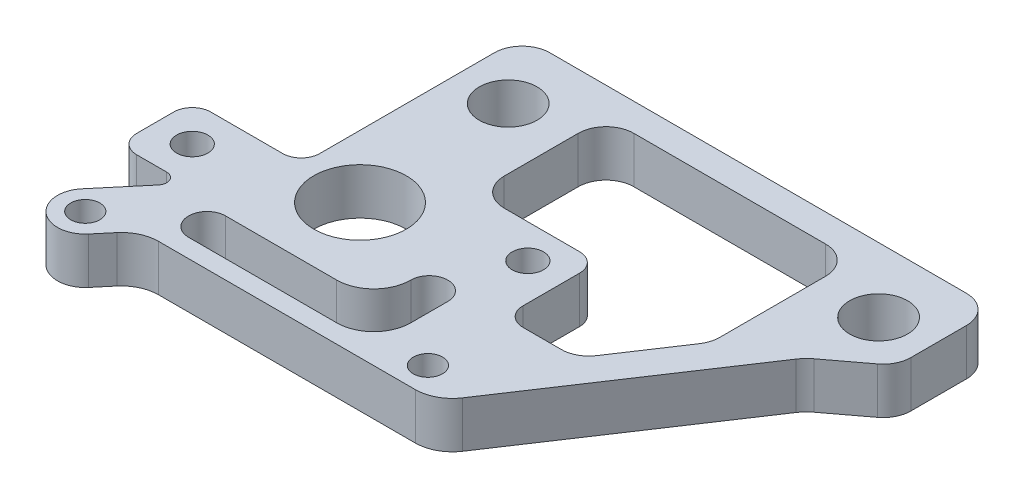
SolidWorks part; units mm, degrees
other "Markup1"
sketch "Sketch6" plane through (-23.3268, 0, -30.7975) normal (-0.0348, 0.9994, -0.0028) x (-0.9993, -0.0348, 0.0153)
sketch "Sketch7" plane through (-23.3268, 0, -30.7975) normal (-0.0348, 0.9994, -0.0028) x (-0.9993, -0.0348, 0.0153)
sketch "Sketch8" plane through (-23.3268, 0, -30.7975) normal (-0.0348, 0.9994, -0.0028) x (-0.9993, -0.0348, 0.0153)
sketch "Sketch10" plane through (-23.3268, 0, -30.7975) normal (-0.0348, 0.9994, -0.0028) x (-0.9993, -0.0348, 0.0153)
sketch "Sketch13" plane through (-23.3268, 0, -30.7975) normal (-0.0348, 0.9994, -0.0028) x (-0.9993, -0.0348, 0.0153)
sketch "Sketch15" plane through (-23.3268, 0, -30.7975) normal (-0.0348, 0.9994, -0.0028) x (-0.9993, -0.0348, 0.0153)
sketch "Sketch16" [suppressed] plane through (-23.3268, 0, -30.7975) normal (-0.0348, 0.9994, -0.0028) x (-0.9993, -0.0348, 0.0153)
sketch "Sketch17" plane through (-23.3268, 0, -30.7975) normal (-0.0348, 0.9994, -0.0028) x (-0.9993, -0.0348, 0.0153)
sketch "Sketch18" plane through (-23.3268, 0, -30.7975) normal (-0.0348, 0.9994, -0.0028) x (-0.9993, -0.0348, 0.0153)
sketch "Sketch19" [suppressed] plane through (-23.3268, 0, -30.7975) normal (-0.0348, 0.9994, -0.0028) x (-0.9993, -0.0348, 0.0153)
sketch "Sketch21" plane through (-23.3268, 0, -30.7975) normal (-0.0348, 0.9994, -0.0028) x (-0.9993, -0.0348, 0.0153)
sketch "Sketch23" plane through (-23.3268, 0, -30.7975) normal (-0.0348, 0.9994, -0.0028) x (-0.9993, -0.0348, 0.0153)
sketch "Sketch24" plane through (-23.3268, 0, -30.7975) normal (-0.0348, 0.9994, -0.0028) x (-0.9993, -0.0348, 0.0153)
sketch "Sketch25" plane through (-23.3268, 0, -30.7975) normal (-0.0348, 0.9994, -0.0028) x (-0.9993, -0.0348, 0.0153)
sketch "Sketch26" [suppressed] plane through (-23.3268, 0, -30.7975) normal (-0.0348, 0.9994, -0.0028) x (-0.9993, -0.0348, 0.0153)
sketch "Sketch27" plane through (-23.3268, 0, -30.7975) normal (-0.0348, 0.9994, -0.0028) x (-0.9993, -0.0348, 0.0153)
sketch "Sketch28" plane through (-23.3268, 0, -30.7975) normal (-0.0348, 0.9994, -0.0028) x (-0.9993, -0.0348, 0.0153)
sketch "Sketch29" plane through (-23.3268, 0, -30.7975) normal (-0.0348, 0.9994, -0.0028) x (-0.9993, -0.0348, 0.0153)
sketch "Sketch30" plane through (-23.3268, 0, -30.7975) normal (-0.0348, 0.9994, -0.0028) x (-0.9993, -0.0348, 0.0153)
sketch "Sketch32" plane through (-23.3268, 0, -30.7975) normal (-0.0348, 0.9994, -0.0028) x (-0.9993, -0.0348, 0.0153)
sketch "Sketch34" [suppressed] plane through (-23.3268, 0, -30.7975) normal (-0.0348, 0.9994, -0.0028) x (-0.9993, -0.0348, 0.0153)
sketch "Sketch35" [suppressed] plane through (-23.3268, 0, -30.7975) normal (-0.0348, 0.9994, -0.0028) x (-0.9993, -0.0348, 0.0153)
sketch "Sketch36" [suppressed] plane through (-23.3268, 0, -30.7975) normal (-0.0348, 0.9994, -0.0028) x (-0.9993, -0.0348, 0.0153)
sketch "Sketch37" plane through (-23.3268, 0, -30.7975) normal (-0.0348, 0.9994, -0.0028) x (-0.9993, -0.0348, 0.0153)
sketch "Sketch38" plane through (-23.3268, 0, -30.7975) normal (-0.0348, 0.9994, -0.0028) x (-0.9993, -0.0348, 0.0153)
sketch "Sketch39" [suppressed] plane through (-23.3268, 0, -30.7975) normal (-0.0348, 0.9994, -0.0028) x (-0.9993, -0.0348, 0.0153)
sketch "Sketch40" plane through (-23.3268, 0, -30.7975) normal (-0.0348, 0.9994, -0.0028) x (-0.9993, -0.0348, 0.0153)
sketch "Sketch41" plane through (-23.3268, 0, -30.7975) normal (-0.0348, 0.9994, -0.0028) x (-0.9993, -0.0348, 0.0153)
sketch "Sketch42" plane through (-23.3268, 0, -30.7975) normal (-0.0348, 0.9994, -0.0028) x (-0.9993, -0.0348, 0.0153)
sketch "Sketch43" plane through (-23.3268, 0, -30.7975) normal (-0.0348, 0.9994, -0.0028) x (-0.9993, -0.0348, 0.0153)
sketch "Sketch44" plane through (-23.3268, 0, -30.7975) normal (-0.0348, 0.9994, -0.0028) x (-0.9993, -0.0348, 0.0153)
sketch "Sketch45" plane through (-23.3268, 0, -30.7975) normal (-0.0348, 0.9994, -0.0028) x (-0.9993, -0.0348, 0.0153)
sketch "Sketch46" plane through (-23.3268, 0, -30.7975) normal (-0.0348, 0.9994, -0.0028) x (-0.9993, -0.0348, 0.0153)
sketch "Sketch47" plane through (-23.3268, 0, -30.7975) normal (-0.0348, 0.9994, -0.0028) x (-0.9993, -0.0348, 0.0153)
sketch "Sketch48" plane through (-23.3268, 0, -30.7975) normal (-0.0348, 0.9994, -0.0028) x (-0.9993, -0.0348, 0.0153)
sketch "Sketch49" plane through (-23.3268, 0, -30.7975) normal (-0.0348, 0.9994, -0.0028) x (-0.9993, -0.0348, 0.0153)
sketch "Sketch50" plane through (-23.3268, 0, -30.7975) normal (-0.0348, 0.9994, -0.0028) x (-0.9993, -0.0348, 0.0153)
sketch "Sketch51" plane through (-23.3268, 0, -30.7975) normal (-0.0348, 0.9994, -0.0028) x (-0.9993, -0.0348, 0.0153)
sketch "Sketch52" [suppressed] plane through (-23.3268, 0, -30.7975) normal (-0.0348, 0.9994, -0.0028) x (-0.9993, -0.0348, 0.0153)
sketch "Sketch53" [suppressed] plane through (-23.3268, 0, -30.7975) normal (-0.0348, 0.9994, -0.0028) x (-0.9993, -0.0348, 0.0153)
sketch "Sketch54" [suppressed] plane through (-23.3268, 0, -30.7975) normal (-0.0348, 0.9994, -0.0028) x (-0.9993, -0.0348, 0.0153)
sketch "Sketch55" [suppressed] plane through (-23.3268, 0, -30.7975) normal (-0.0348, 0.9994, -0.0028) x (-0.9993, -0.0348, 0.0153)
sketch "Sketch56" plane through (-23.3268, 0, -30.7975) normal (-0.0348, 0.9994, -0.0028) x (-0.9993, -0.0348, 0.0153)
sketch "Sketch57" plane through (-23.3268, 0, -30.7975) normal (-0.0348, 0.9994, -0.0028) x (-0.9993, -0.0348, 0.0153)
sketch "Sketch58" plane through (-23.3268, 0, -30.7975) normal (-0.0348, 0.9994, -0.0028) x (-0.9993, -0.0348, 0.0153)
sketch "Sketch59" plane through (-23.3268, 0, -30.7975) normal (-0.0348, 0.9994, -0.0028) x (-0.9993, -0.0348, 0.0153)
sketch "Sketch60" plane through (-23.3268, 0, -30.7975) normal (-0.0348, 0.9994, -0.0028) x (-0.9993, -0.0348, 0.0153)
sketch "Sketch61" plane through (-23.3268, 0, -30.7975) normal (-0.0348, 0.9994, -0.0028) x (-0.9993, -0.0348, 0.0153)
sketch "Sketch62" [suppressed] plane through (-23.3268, 0, -30.7975) normal (-0.0348, 0.9994, -0.0028) x (-0.9993, -0.0348, 0.0153)
sketch "Sketch63" [suppressed] plane through (-23.3268, 0, -30.7975) normal (-0.0348, 0.9994, -0.0028) x (-0.9993, -0.0348, 0.0153)
sketch "Sketch64" plane through (-24.0303, 0, -30.7975) normal (-0.0348, 0.9994, -0.0028) x (-0.9993, -0.0348, 0.0153)
sketch "Sketch65" plane through (-24.0303, 0, -30.7975) normal (-0.0348, 0.9994, -0.0028) x (-0.9993, -0.0348, 0.0153)
sketch "Sketch66" plane through (-24.0303, 0, -30.7975) normal (-0.0348, 0.9994, -0.0028) x (-0.9993, -0.0348, 0.0153)
sketch "Sketch67" [suppressed] plane through (-24.0303, 0, -30.7975) normal (-0.0348, 0.9994, -0.0028) x (-0.9993, -0.0348, 0.0153)
sketch "Sketch68" plane through (-24.0303, 0, -30.7975) normal (-0.0348, 0.9994, -0.0028) x (-0.9993, -0.0348, 0.0153)
sketch "Sketch69" plane through (-24.0303, 0, -30.7975) normal (-0.0348, 0.9994, -0.0028) x (-0.9993, -0.0348, 0.0153)
sketch "Sketch70" plane through (-24.0303, 0, -30.7975) normal (-0.0348, 0.9994, -0.0028) x (-0.9993, -0.0348, 0.0153)
sketch "Sketch71" plane through (-24.0303, 0, -30.7975) normal (-0.0348, 0.9994, -0.0028) x (-0.9993, -0.0348, 0.0153)
sketch "Sketch72" plane through (-24.0303, 0, -30.7975) normal (-0.0348, 0.9994, -0.0028) x (-0.9993, -0.0348, 0.0153)
sketch "Sketch73" [suppressed] plane through (-23.3268, 0, -30.7975) normal (-0.0348, 0.9994, -0.0028) x (-0.9993, -0.0348, 0.0153)
sketch "Sketch74" [suppressed] plane through (-24.0303, 0, -30.7975) normal (-0.0348, 0.9994, -0.0028) x (-0.9993, -0.0348, 0.0153)
sketch "Sketch75" [suppressed] plane through (-24.0303, 0, -30.7975) normal (-0.0348, 0.9994, -0.0028) x (-0.9993, -0.0348, 0.0153)
sketch "Sketch76" [suppressed] plane through (-24.0303, 0, -30.7975) normal (-0.0348, 0.9994, -0.0028) x (-0.9993, -0.0348, 0.0153)
sketch "Sketch77" plane through (-24.0303, 0, -30.7975) normal (-0.0348, 0.9994, -0.0028) x (-0.9993, -0.0348, 0.0153)
sketch "Sketch78" plane through (-23.5217, 0, -30.7975) normal (-0.0348, 0.9994, -0.0028) x (-0.9993, -0.0348, 0.0153)
sketch "Sketch79" plane through (-23.5217, 0, -30.7975) normal (-0.0348, 0.9994, -0.0028) x (-0.9993, -0.0348, 0.0153)
material "6061-T6 (SS)"
ref_plane "X-Y Datum" through (0, 0, 0) normal (0, 0, 1) x (1, 0, 0)
ref_plane "X-Z Datum" through (0, 0, 0) normal (0, 1, 0) x (1, 0, 0)
ref_plane "Y-Z Datum" through (0, 0, 0) normal (1, 0, 0) x (0, 0, -1)
other "Graphic1"
other "Graphic (Closed) -1"
other "Graphic (Closed) -2"
sketch "Sketch2" plane through (0, 0, 0) normal (0, 1, 0) x (1, 0, 0)
  line L0 (48.6426, -18.7325) -> (-23.0162, -18.7325)
  line L1 (24.0125, -14.7036) -> (25.7865, -13.7801) construction
  line L2 (0, 0) -> (105.5557, -202.7707) construction
  line L3 (11.142, -21.4036) -> (-3.5026, -29.027) construction
  line L4 (0, 0) -> (0, -121.3797) construction
  line L5 (-3.5026, -29.027) -> (90.9112, -210.3941) construction
  line L6 (90.9112, -210.3941) -> (105.5557, -202.7707) construction
  line L7 (11.142, -21.4036) -> (24.0125, -14.7036) construction
  line L11 (-12.7, 30.7975) -> (57.15, 30.7975)
  line L12 (57.15, 13.0175) -> (57.15, 30.7975)
  line L13 (57.15, 13.0175) -> (-12.7, 13.0175) construction
  line L15 (44.7685, -18.0975) -> (44.7685, -11.3157) construction
  line L16 (44.7685, -18.0975) -> (34.8625, -18.0975) construction
  line L18 (44.7685, 9.8425) -> (34.8625, 9.8425) construction
  line L20 (44.7685, -11.3157) -> (49.8485, -11.3157) construction
  line L21 (49.8485, -11.3157) -> (49.8485, 3.0607) construction
  line L22 (49.8485, 3.0607) -> (44.7685, 3.0607) construction
  line L23 (44.7685, 3.0607) -> (44.7685, 9.8425) construction
  line L24 (34.8625, -18.0975) -> (34.8625, 9.8425) construction
  line L25 (48.6426, -18.7325) -> (57.15, 13.0175)
  line L26 (-12.7, 30.7975) -> (-12.7, 13.0175)
  line L28 (-12.5603, 0) -> (-16.51, -40.5272) construction
  line L30 (-23.0162, -18.7325) -> (-12.7, 13.0175)
  circle A0 centre (0, 0) radius 3.175
  circle A1 centre (24.0125, -14.7036) radius 2
  circle A2 centre (-1.5875, 21.9075) radius 3.9688
  circle A3 centre (49.2125, 21.9075) radius 3.9687
  circle A4 centre (39.8485, -4.1275) radius 5.1
  circle A5 centre (24.0125, -14.7036) radius 3.175 construction
  circle A6 centre (39.8485, -14.6275) radius 1.6
  circle A7 centre (39.8485, 6.3725) radius 1.6
  circle A8 centre (-17.2047, -14.9225) radius 3.175 construction
  circle A9 centre (-17.2047, -14.9225) radius 2
  point P9 (11.142, -21.4036)
  point P30 (49.8485, -4.1275)
  point P31 (34.8625, -4.1275)
  dimension "D1" = 6.35
  dimension "D8" = 4
  dimension "D10" = 7.9375
  dimension "D11" = 7.9375
  dimension "D16" = 27.94
  dimension "D23" = 10.2
  dimension "D20" = 6.35
  dimension "D30" = 3.2
  dimension "D32" = 3.2
  dimension "D34" = 6.35
  dimension "D35" = 4
  dimension "D3" = 13.0175
  dimension "D4" = 16.51
  dimension "D5" = 228.6
  dimension "D6" = 24.13
  dimension "D7" = 27.5
  dimension "D9" = 16.51
  dimension "D12" = 8.89
  dimension "D13" = 69.85
  dimension "D14" = 7.9375
  dimension "D15" = 31.75
  dimension "D17" = 17.78
  dimension "D18" = 3.175
  dimension "D19" = 14.986
  dimension "D21" = 5.08
  dimension "D22" = 14.3764
  dimension "D24" = 10
  dimension "D25" = 36.83
  dimension "D26" = 50.8
  dimension "D27" = 165
  dimension "D28" = 12.7
  dimension "D29" = 17.3015
  dimension "D31" = 10.5
  dimension "D33" = 10.5
  dimension "D36" = 162
extrude "Boss-Extrude1" [suppressed] add sketch "Sketch2" against normal blind 6.35
ref_point "Point1" [suppressed]
sketch "Sketch3" [suppressed] plane through (0, 0, 0) normal (0, 1, 0) x (1, 0, 0)
  line L0 (39.9681, 6.3725) -> (39.9681, -4.1275) construction
  line L1 (57.2697, 12.9663) -> (-12.5803, 12.9663) construction
  line L5 (39.9681, -4.1275) -> (39.9681, -14.6275) construction
  line L6 (42.0297, -18.7325) -> (20.4164, -18.7325)
  line L7 (57.2697, 12.9663) -> (57.2697, 30.7975)
  line L8 (57.2697, 30.7975) -> (-12.5803, 30.7975)
  line L9 (-12.5803, 30.7975) -> (-12.5803, 12.9663)
  line L10 (40.938, 24.6176) -> (16.9472, 10.7666)
  line L11 (13.3942, 11.8528) -> (6.9035, 25.1608)
  line L12 (8.045, 26.9875) -> (40.303, 26.9875)
  line L13 (57.2697, 12.9663) -> (48.3797, 12.9663)
  line L14 (48.3797, 12.9663) -> (48.3797, -12.3825)
  line L16 (-23.0162, -18.7325) -> (48.6426, -18.7325) construction
  line L18 (16.6064, -14.8627) -> (10.2787, -14.8627)
  line L21 (-8.965, -15.5427) -> (-15.106, -18.7325)
  line L24 (-21.1701, -13.6017) -> (-12.5803, 12.9663)
  line L29 (17.8764, -16.1925) -> (17.8764, -16.1327)
  circle A0 centre (0.1197, 0) radius 3.175
  circle A1 centre (-1.4678, 21.9075) radius 3.9688
  circle A2 centre (49.3322, 21.9075) radius 3.9687
  circle A3 centre (39.9681, -4.1275) radius 5.1
  circle A4 centre (39.9681, -14.6275) radius 1.6
  circle A5 centre (39.9681, 6.3725) radius 1.6
  circle A6 centre (24.1322, -14.7036) radius 2
  circle A7 centre (-17.085, -14.9225) radius 2
  arc A8 (13.3942, 11.8528) -> (16.9472, 10.7666) centre (15.6772, 12.9663) ccw
  arc A9 (8.045, 26.9875) -> (6.9035, 25.1608) centre (8.045, 25.7175) ccw
  arc A10 (40.938, 24.6176) -> (40.303, 26.9875) centre (40.303, 25.7175) ccw
  arc A11 (10.2787, -14.8627) -> (-8.965, -15.5427) centre (0.1197, 0) cw
  arc A12 (-15.106, -18.7325) -> (-21.1701, -13.6017) centre (-17.085, -14.9225) cw
  arc A13 (42.0297, -18.7325) -> (48.3797, -12.3825) centre (42.0297, -12.3825) ccw
  arc A14 (20.4164, -18.7325) -> (17.8764, -16.1925) centre (20.4164, -16.1925) cw
  arc A15 (16.6064, -14.8627) -> (17.8764, -16.1327) centre (16.6064, -16.1327) cw
  dimension "D1" = 6.35
  dimension "D4" = 7.9375
  dimension "D9" = 10.2
  dimension "D10" = 3.2
  dimension "D11" = 4
  dimension "D21" = 2.54
  dimension "D22" = 1.27
  dimension "D3" = 6.35
  dimension "D28" = 2.54
  dimension "D29" = 1.27
  dimension "D2" = 7.9375
  dimension "D5" = 50.8
  dimension "D6" = 21.9075
  dimension "D7" = 1.5875
  dimension "D8" = 8.89
  dimension "D12" = 10.5
  dimension "D13" = 17.2047
  dimension "D14" = 24.0125
  dimension "D15" = 14.7036
  dimension "D16" = 39.8485
  dimension "D17" = 4.1275
  dimension "D18" = 14.9225
  dimension "D19" = 69.85
  dimension "D20" = 3.81
  dimension "D23" = 30
  dimension "D24" = 64
  dimension "D25" = 32.258
  dimension "D26" = 15.5575
  dimension "D27" = 25.3488
  dimension "D30" = 8.89
sketch "Sketch4" plane through (0, 0, 0) normal (0, 1, 0) x (1, 0, 0)
  line L0 (39.8485, 6.3725) -> (39.8485, -4.1275) construction
  line L1 (56.1975, 13.0175) -> (-8.5725, 13.0175) construction
  line L2 (39.8485, -4.1275) -> (39.8485, -14.6275) construction
  line L3 (28.7355, -18.4375) -> (22.4839, -18.4375)
  line L5 (52.3875, 30.7975) -> (-4.7625, 30.7975)
  line L6 (-8.5725, 26.9875) -> (-8.5725, 12.6075)
  line L43 (48.9856, 12.0279) -> (54.6804, 16.3193)
  line L44 (56.1975, 19.3621) -> (56.1975, 26.9875)
  line L50 (-17.3145, -25.274) -> (-23.148, -20.3714)
  line L59 (0, 0) -> (0, 5.6144) construction
  line L64 (48.9856, 12.0279) -> (28.7355, -18.4375)
  line L65 (6.7496, 26.9875) -> (40.693, 26.9875)
  line L66 (6.7496, 26.9875) -> (6.7496, 9.2075)
  line L70 (33.289, -3.6663) -> (40.693, 7.4726)
  line L74 (40.693, 26.9875) -> (40.693, 7.4726)
  line L75 (6.7496, 9.2075) -> (23.453, 9.2075)
  line L77 (-11.5691, -18.4375) -> (-17.3145, -25.274)
  line L78 (-23.5217, 0.508) -> (-8.5725, 0.508)
  line L79 (-8.5725, 0.508) -> (-8.5725, 12.6075)
  line L82 (23.453, 9.2075) -> (23.453, -3.6663)
  line L83 (23.453, -3.6663) -> (33.289, -3.6663)
  line L85 (-14.1393, -9.652) -> (-23.148, -20.3714)
  line L86 (-23.5217, 0.508) -> (-23.5217, -9.652)
  line L88 (-23.5217, -9.652) -> (-14.1393, -9.652)
  line L89 (18.4417, 4.572) -> (-18.4417, -4.572)
  line L90 (22.4839, -18.4375) -> (-11.5691, -18.4375)
  line L91 (-7.62, -13.3575) -> (15.24, -13.3575) construction
  line L92 (-7.62, -10.8175) -> (15.24, -10.8175)
  line L93 (-7.62, -15.8975) -> (15.24, -15.8975)
  line L94 (15.24, -13.3575) -> (15.24, -5.7375) construction
  line L95 (12.7, -13.3575) -> (12.7, -5.7375)
  line L96 (17.78, -13.3575) -> (17.78, -5.7375)
  line L97 (17.78, -13.3575) -> (17.78, -15.8975)
  line L98 (17.78, -15.8975) -> (15.24, -15.8975)
  circle A0 centre (0, 0) radius 6.35
  circle A1 centre (-1.5875, 21.9075) radius 3.9688
  circle A2 centre (49.2125, 21.9075) radius 3.9687
  circle A6 centre (24.0125, -14.7036) radius 2
  circle A7 centre (-17.78, -19.906) radius 2
  arc A19 (-8.5725, 26.9875) -> (-4.7625, 30.7975) centre (-4.7625, 26.9875) cw
  arc A20 (52.3875, 30.7975) -> (56.1975, 26.9875) centre (52.3875, 26.9875) cw
  circle A33 centre (24.0125, -14.7036) radius 3.5 construction
  arc A45 (56.1975, 19.3621) -> (54.6804, 16.3193) centre (52.3875, 19.3621) cw
  circle A55 centre (0, 0) radius 19 construction
  circle A57 centre (18.4417, 4.572) radius 2.1463
  circle A58 centre (-18.4417, -4.572) radius 2.1463
  arc A59 (-7.62, -10.8175) -> (-7.62, -15.8975) centre (-7.62, -13.3575) ccw
  arc A60 (17.78, -13.3575) -> (15.24, -10.8175) centre (15.24, -13.3575) ccw
  arc A61 (12.7, -13.3575) -> (17.78, -13.3575) centre (15.24, -13.3575) ccw
  arc A62 (17.78, -5.7375) -> (12.7, -5.7375) centre (15.24, -5.7375) ccw
  point P21 (3.81, -13.3575)
  point P36 (9.3466, -11.4637)
  point P43 (15.24, -9.5475)
  point P49 (-17.78, -19.906)
  point P58 (-8.5725, 30.7975)
  point P66 (15.24, -12.0875)
  point P67 (0, 0)
  point P77 (56.1975, 17.4625)
  dimension "D1" = 12.7
  dimension "D2" = 7.9375
  dimension "D7" = 10.16
  dimension "D8" = 4
  dimension "D19" = 17.24
  dimension "D20" = 6.9738
  dimension "D25" = 3.81
  dimension "D26" = 7
  dimension "D27" = 22.86
  dimension "D31" = 4.2926
  dimension "D33" = 3.81
  dimension "D37" = 5.08
  dimension "D38" = 4.572
  dimension "D39" = 15.5045
  dimension "D48" = 17.78
  dimension "D49" = 5.08
  dimension "D50" = 7.62
  dimension "D51" = 13.97
  dimension "D23" = 3.81
  dimension "D32" = 3.81
  dimension "D46" = 5.08
  dimension "D47" = 19.906
  dimension "D45" = 3.81
  dimension "D18" = 17.78
  dimension "D29" = 5.08
  dimension "D30" = 38
  dimension "D34" = 12.8738
  dimension "D35" = 4.3845
  dimension "D41" = 33.9434
  dimension "D42" = 5.08
  dimension "D43" = 3.81
  dimension "D44" = 4.572
  dimension "D15" = 3.81
  dimension "D53" = 2.54
  dimension "D3" = 50.8
  dimension "D4" = 21.9075
  dimension "D5" = 1.5875
  dimension "D9" = 10.5
  dimension "D10" = 24.0125
  dimension "D11" = 14.7036
  dimension "D12" = 39.8485
  dimension "D13" = 4.1275
  dimension "D14" = 3.81
  dimension "D16" = 6.985
  dimension "D17" = 8.89
  dimension "D21" = 17.78
  dimension "D22" = 40.3046
  dimension "D24" = 236.388
  dimension "D28" = 30.4654
  dimension "D36" = 9.525
  dimension "D40" = 127
  dimension "D52" = 6.35
  dimension "D60" = 6.985
extrude "Boss-Extrude2" add sketch "Sketch4" against normal blind 6.35
ref_point "Point2"
ref_point "Point3"
ref_point "Point4"
other "Graphic2" [suppressed]
other "Graphic (Closed) -3"
other "Graphic (Closed) -4"
other "Graphic (Closed) -5"
fillet "Fillet1" radius 5.08 2 edges at (48.9856, -3.175, -12.0279) (28.7355, -3.175, 18.4375)
fillet "Fillet7" radius 3.81 4 edges at (6.7496, -3.175, -9.2075) (40.693, -3.175, -7.4726) (40.693, -3.175, -26.9875) (6.7496, -3.175, -26.9875)
fillet "Fillet9" radius 5.08 3 edges at (-11.5691, -3.175, 18.4375) (12.7, -3.175, 10.8175) (17.78, -3.175, 15.8975)
fillet "Fillet10" radius 1.27 1 edges at (-14.1393, -3.175, 9.652)
fillet "Fillet11" radius 3.81 2 edges at (-17.3145, -3.175, 25.274) (-23.148, -3.175, 20.3714)
fillet "Fillet12" radius 2.54 5 edges at (23.453, -3.175, 3.6663) (23.453, -3.175, -9.2075) (-8.5725, -3.175, -0.508) (-23.5217, -3.175, -0.508) (-23.5217, -3.175, 9.652)
fillet "Fillet13" radius 3.81 1 edges at (33.289, -3.175, 3.6663)
